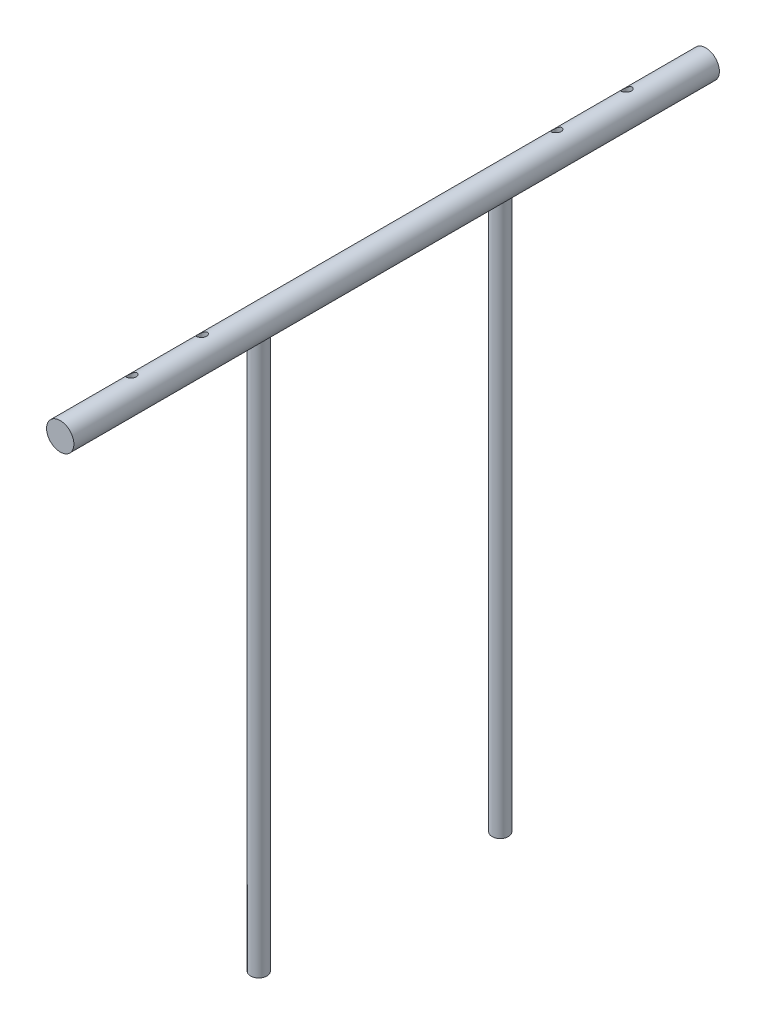
SolidWorks part; units mm, degrees
ref_plane "Front Plane" through (0, 0, 0) normal (0, 0, 1) x (1, 0, 0)
ref_plane "Top Plane" through (0, 0, 0) normal (0, 1, 0) x (1, 0, 0)
ref_plane "Right Plane" through (0, 0, 0) normal (1, 0, 0) x (0, 0, -1)
sketch "Sketch2" plane through (0, 0, 0) normal (1, 0, 0) x (0, 0, -1)
  line L0 (-291.1354, 1.7348) -> (-291.1354, 2388.5751) construction
  line L1 (-526.1133, 1496.9266) -> (100, 1496.9266) construction
  line L2 (100, 1496.9266) -> (300, 1496.9266) construction
  line L3 (-526.1133, 1496.9266) -> (-882.2708, 1496.9266) construction
  line L4 (0, 1496.9266) -> (0, 1424.4364)
  line L5 (200, 1496.9266) -> (200, 1424.4364)
  line L6 (-782.2708, 1496.9266) -> (-782.2708, 1424.4364)
  line L7 (-446.1354, 1.7348) -> (-136.1911, 1.7348) construction
  line L8 (-446.1354, 1.7348) -> (-291.1354, 1.7348)
  line L9 (-291.1354, 1.7348) -> (-291.1354, -313.314) construction
  line L10 (-582.2708, 1496.9266) -> (-582.2708, 1424.4364)
  line L11 (-882.2708, 1496.9266) -> (-782.2708, 1496.9266)
  line L12 (-291.1354, 1.7348) -> (-291.1354, 2483.1276)
  point P10 (-882.2708, 1496.9266)
  dimension "D1" = 200
  dimension "D2" = 100
  dimension "D3" = 291.1354
  dimension "D6" = 155
sketch "Sketch4" plane through (0, 0, 0) normal (1, 0, 0) x (0, 0, -1)
  line L2 (-526.1133, 1496.9266) -> (100, 1496.9266) construction
  line L4 (-429.3892, 1496.9266) -> (-429.3892, 1068.7186)
  line L6 (-154.9951, 1068.7186) -> (-159.2435, 1496.9266)
  line L7 (-882.2708, 1496.9266) -> (300, 1496.9266)
  line L8 (300, 1496.9266) -> (300, 1536.1866)
  line L9 (300, 1536.1866) -> (-882.2708, 1536.1866)
  line L10 (-882.2708, 1536.1866) -> (-882.2708, 1496.9266)
  line L13 (-429.3892, 1496.9266) -> (-397.1243, 1496.9266)
  line L14 (-429.3892, 1496.9266) -> (-397.1243, 1496.9266)
  line L15 (-429.3892, 1496.9266) -> (-397.1243, 1496.9266)
  line L16 (-429.3892, 1068.7186) -> (-397.1243, 1068.7186)
  line L17 (-429.3892, 1282.8226) -> (-397.1243, 1282.8226)
  line L18 (-414.3892, 1496.9266) -> (-414.3892, 1083.7186)
  line L19 (-414.3892, 1083.7186) -> (-414.3892, 1068.7186)
  line L22 (-414.3892, 1083.7186) -> (-397.1243, 1083.7186) construction
  dimension "D1" = 15
extrude "Boss-Extrude1" add sketch "Sketch4" along normal blind 15 separate body contours L9 L10 L7 L8 region at (0, 1516.5566, 291.1354)
sketch "Sketch5" plane through (0, 0, 882.2708) normal (0, 0, 1) x (1, 0, 0)
  line L0 (7.5, 1536.1866) -> (7.5, 1496.9266) construction
  line L1 (15, 1536.1866) -> (0, 1536.1866) construction
  line L2 (15, 1496.9266) -> (0, 1496.9266) construction
  line L3 (15, 1516.5566) -> (0, 1516.5566) construction
  line L4 (15, 1536.1866) -> (15, 1496.9266) construction
  line L5 (0, 1.7348) -> (0, 2388.5751) construction
  circle A0 centre (7.5, 1516.5566) radius 25
extrude "Boss-Extrude2" add sketch "Sketch5" against normal up to vertex (1182.2708 mm away) up to point (15, 1496.9266, -300)
ref_plane "Plane1" through (0, 1495, 0) normal (0, -1, 0) x (-1, 0, 0)
sketch "Sketch7" plane through (0, 1495, 0) normal (0, -1, 0) x (-1, 0, 0)
  line L0 (0, -526.1133) -> (0, -882.2708) construction
  line L1 (0, -782.2708) -> (0, -743.4263)
  line L2 (0, -882.2708) -> (0, -782.2708) construction
  line L3 (0, -575.8283) -> (0, -614.6728)
  circle A0 centre (0, -614.6728) radius 8
  circle A1 centre (0, -743.4263) radius 8
extrude "Cut-Extrude3" cut sketch "Sketch7" against normal through all both and the other way through all contours A1 | A0
ref_plane "Plane2" through (0, 0, 290) normal (0, 0, 1) x (1, 0, 0)
mirror "Mirror2" about plane through (0, 0, 290) normal (0, 0, 1) of "Cut-Extrude3"
sketch "Sketch8" plane through (0, 0, 0) normal (1, 0, 0) x (0, 0, -1)
  line L0 (-526.1133, 1496.9266) -> (-526.1133, 1028.6351)
  line L1 (-526.1133, 1028.6351) -> (-511.1133, 1028.6351)
  line L2 (-511.1133, 1028.6351) -> (-511.1133, 1496.9266)
  line L3 (-526.1133, 1496.9266) -> (100, 1496.9266) construction
  line L4 (-290, 202.3822) -> (-290, -202.3822) construction
  line L5 (-53.8867, 1028.6351) -> (-68.8867, 1028.6351)
  line L6 (-53.8867, 1496.9266) -> (-53.8867, 1028.6351)
  line L7 (-68.8867, 1028.6351) -> (-68.8867, 1496.9266)
  line L8 (-526.1133, 1496.9266) -> (-511.1133, 1496.9266)
  line L9 (-68.8867, 1496.9266) -> (-53.8867, 1496.9266)
  dimension "D1" = 15
revolve "Revolve3" add sketch "Sketch8" angle 360 about L7 region at (0, 1262.7809, 61.3867)
mirror "Mirror3" about plane through (0, 0, 290) normal (0, 0, 1) of "Revolve3"
sketch "Sketch12" plane through (0, 1028.6351, 0) normal (0, -1, 0) x (1, 0, 0)
  circle A0 centre (0, 511.1133) radius 15
extrude "Boss-Extrude3" add sketch "Sketch12" along normal blind 550
sketch "Sketch13" plane through (0, 1028.6351, 0) normal (0, -1, 0) x (1, 0, 0)
  circle A0 centre (0, 68.8867) radius 15
extrude "Boss-Extrude4" add sketch "Sketch13" along normal blind 550
